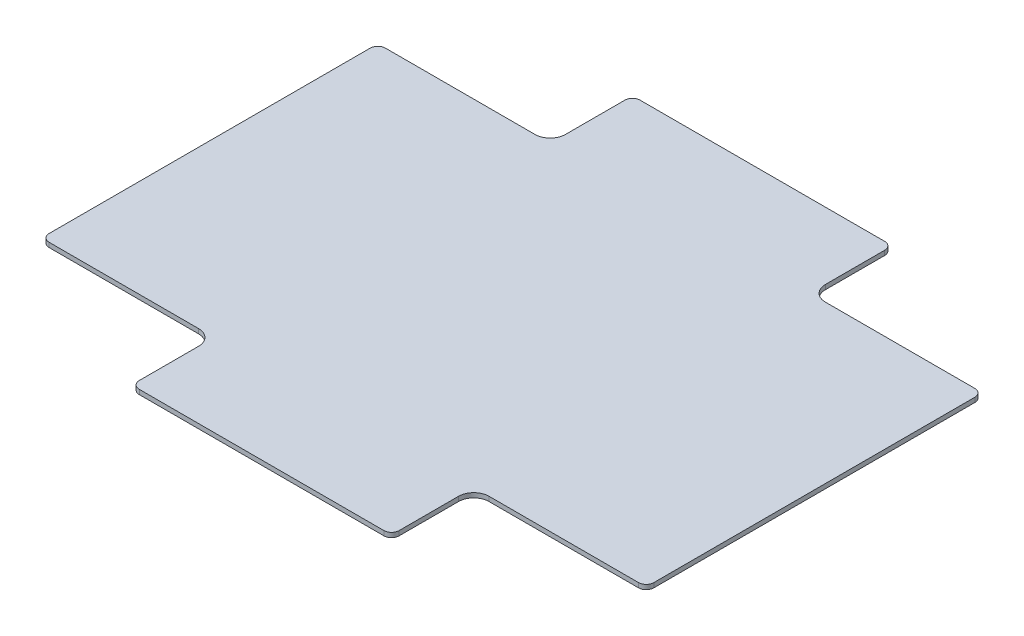
SolidWorks part; units mm, degrees
material "7075-T6, Пластина (SS)"
ref_plane "Спереди" through (0, 0, 0) normal (0, 0, 1) x (1, 0, 0)
ref_plane "Сверху" through (0, 0, 0) normal (0, 1, 0) x (1, 0, 0)
ref_plane "Справа" through (0, 0, 0) normal (1, 0, 0) x (0, 0, -1)
sketch "Эскиз1" plane through (0, 0, 0) normal (0, 1, 0) x (1, 0, 0)
  line L1 (-80, -163.8055) -> (80, -163.8055)
  line L2 (-197.7687, -105) -> (-197.7687, 105)
  line L3 (-80, 163.8055) -> (80, 163.8055)
  line L4 (197.7687, -105) -> (197.7687, 105)
  line L5 (-236.4266, 144.4996) -> (-147.9018, 144.4996) construction
  line L6 (-147.9018, 144.4996) -> (286.4952, 144.4996) construction
  line L18 (-284.5497, 0) -> (284.3305, 0) construction
  line L19 (-160.9018, 110) -> (-134.9018, 110)
  line L20 (-160.9018, 110) -> (-160.9018, 0)
  line L21 (-160.9018, 0) -> (-134.9018, 0)
  line L22 (-134.9018, 110) -> (-134.9018, 0)
  line L23 (-147.9018, -182.6295) -> (-147.9018, 219.9923) construction
  line L24 (-160.9018, 0) -> (-134.9018, 0)
  line L25 (-160.9018, 0) -> (-160.9018, -110)
  line L26 (-160.9018, -110) -> (-134.9018, -110)
  line L27 (-134.9018, 0) -> (-134.9018, -110)
  line L28 (-97.9018, -119.4996) -> (-197.9018, -119.4996)
  line L29 (-97.9018, 169.4996) -> (-197.9018, 169.4996)
  line L30 (-97.9018, 169.4996) -> (-97.9018, 119.4996)
  line L31 (-97.9018, 119.4996) -> (-197.9018, 119.4996)
  line L32 (-197.9018, 169.4996) -> (-197.9018, 119.4996)
  line L33 (-97.9018, 169.4996) -> (-197.9018, 119.4996) construction
  line L34 (-97.9018, 119.4996) -> (-197.9018, 169.4996) construction
  line L35 (-197.9018, -169.4996) -> (-197.9018, -119.4996)
  line L36 (-97.9018, -169.4996) -> (-197.9018, -169.4996)
  line L37 (-97.9018, -169.4996) -> (-97.9018, -119.4996)
  line L39 (-85, 120) -> (-85, 158.8055)
  line L40 (0, 262.7398) -> (0, -186.5795) construction
  line L41 (-192.7687, 110) -> (-95, 110)
  line L43 (-192.7687, -110) -> (-95, -110)
  line L44 (-85, -120) -> (-85, -158.8055)
  line L45 (85, 120) -> (85, 158.8055)
  line L46 (192.7687, 110) -> (95, 110)
  line L47 (192.7687, -110) -> (95, -110)
  line L48 (85, -120) -> (85, -158.8055)
  line L49 (97.9018, -169.4996) -> (97.9018, -119.4996)
  line L50 (97.9018, -169.4996) -> (197.9018, -169.4996)
  line L51 (197.9018, -169.4996) -> (197.9018, -119.4996)
  line L52 (97.9018, -119.4996) -> (197.9018, -119.4996)
  line L53 (160.9018, 0) -> (160.9018, -110)
  line L54 (160.9018, -110) -> (134.9018, -110)
  line L55 (134.9018, 0) -> (134.9018, -110)
  line L56 (160.9018, 0) -> (134.9018, 0)
  line L57 (160.9018, 110) -> (160.9018, 0)
  line L58 (160.9018, 0) -> (134.9018, 0)
  line L59 (134.9018, 110) -> (134.9018, 0)
  line L60 (160.9018, 110) -> (134.9018, 110)
  line L61 (97.9018, 119.4996) -> (197.9018, 119.4996)
  line L62 (197.9018, 169.4996) -> (197.9018, 119.4996)
  line L63 (97.9018, 169.4996) -> (197.9018, 169.4996)
  line L64 (97.9018, 169.4996) -> (97.9018, 119.4996)
  arc A0 (85, -120) -> (95, -110) centre (95, -120) cw
  arc A1 (85, 120) -> (95, 110) centre (95, 120) ccw
  arc A2 (-95, -110) -> (-85, -120) centre (-95, -120) cw
  arc A3 (-85, 120) -> (-95, 110) centre (-95, 120) cw
  arc A4 (192.7687, -110) -> (197.7687, -105) centre (192.7687, -105) ccw
  arc A5 (85, -158.8055) -> (80, -163.8055) centre (80, -158.8055) cw
  arc A6 (-85, -158.8055) -> (-80, -163.8055) centre (-80, -158.8055) ccw
  arc A7 (-192.7687, -110) -> (-197.7687, -105) centre (-192.7687, -105) cw
  arc A8 (-192.7687, 110) -> (-197.7687, 105) centre (-192.7687, 105) ccw
  arc A9 (197.7687, 105) -> (192.7687, 110) centre (192.7687, 105) ccw
  arc A10 (85, 158.8055) -> (80, 163.8055) centre (80, 158.8055) ccw
  arc A11 (-85, 158.8055) -> (-80, 163.8055) centre (-80, 158.8055) cw
  point P0 (0, 0)
  point P3 (85, -110)
  point P17 (-147.9018, 110)
  point P18 (-147.9018, 110)
  point P20 (-147.9018, 0)
  point P22 (-150, 134)
  point P37 (-147.9018, 144.4996)
  point P46 (85, 110)
  point P52 (-85, -110)
  point P55 (-85, 110)
  point P56 (-147.9018, 0)
  point P77 (197.7687, -110)
  point P80 (85, -163.8055)
  point P83 (-85, -163.8055)
  point P86 (-197.7687, -110)
  point P89 (-197.7687, 110)
  point P92 (197.7687, 110)
  point P95 (85, 163.8055)
  point P98 (-85, 163.8055)
  dimension "D2" = 50
  dimension "D6" = 10
  dimension "D4" = 5
  dimension "D3" = 26
  dimension "D5" = 338.9991
  dimension "D7" = 395.5373
  dimension "D8" = 110
  dimension "D9" = 170
  dimension "D10" = 100
  dimension "D13" = 9.4996
  dimension "D14" = 12.9018
sketch "Эскиз2" plane through (0, 0, 0) normal (0, 1, 0) x (1, 0, 0)
  line L0 (-162.9105, 114) -> (-136.9105, 114)
  line L1 (-162.9105, 114) -> (-162.9105, 0)
  line L2 (-162.9105, 0) -> (-136.9105, 0)
  line L3 (-136.9105, 114) -> (-136.9105, 0)
  line L4 (-149.9105, -192.6295) -> (-149.9105, 209.9923) construction
  line L5 (-162.9105, 0) -> (-136.9105, 0)
  line L6 (-162.9105, 0) -> (-162.9105, -114)
  line L7 (-162.9105, -114) -> (-136.9105, -114)
  line L8 (-136.9105, 0) -> (-136.9105, -114)
  line L9 (-99.9105, -123.5568) -> (-199.9105, -123.5568)
  line L10 (-99.9105, 163.4996) -> (-199.9105, 163.4996)
  line L11 (-99.9105, 163.4996) -> (-99.9105, 123.4996)
  line L12 (-99.9105, 123.4996) -> (-199.9105, 123.4996)
  line L13 (-199.9105, 163.4996) -> (-199.9105, 123.4996)
  line L14 (-199.9105, -163.5568) -> (-199.9105, -123.5568)
  line L15 (-99.9105, -163.5568) -> (-199.9105, -163.5568)
  line L16 (-99.9105, -163.5568) -> (-99.9105, -123.5568)
  line L17 (-284.5497, 0) -> (284.3305, 0) construction
  point P11 (-149.9105, 0)
  point P12 (-149.9105, 0)
sketch "Эскиз3" plane through (0, 0, 0) normal (0, 1, 0) x (1, 0, 0)
  line L0 (-89.8176, -177.9027) -> (70.2405, -177.9027)
  line L1 (-209.7886, -106.9112) -> (-209.7886, 106.8353)
  line L2 (-80.029, 172.0973) -> (50.2405, 172.0973)
  line L3 (170.2114, -106.9112) -> (170.2114, 103.9123)
  line L4 (-87.1938, 124.0033) -> (-87.1938, 164.9326)
  line L5 (-202.6239, 114) -> (-97.1971, 114)
  line L6 (-202.6239, -114.076) -> (-106.9857, -114.076)
  line L7 (-96.9823, -124.0793) -> (-96.9823, -170.738)
  line L8 (57.4052, 121.0803) -> (57.4052, 164.9326)
  line L9 (163.0467, 111.077) -> (67.4085, 111.077)
  line L10 (163.0467, -114.076) -> (87.4085, -114.076)
  line L11 (77.4052, -124.0793) -> (77.4052, -170.738)
  line L13 (-162.9105, 114) -> (-136.9105, 114) construction
  arc A0 (77.4052, -124.0793) -> (87.4085, -114.076) centre (87.4085, -124.0793) cw
  arc A1 (57.4052, 121.0803) -> (67.4085, 111.077) centre (67.4085, 121.0803) ccw
  arc A2 (-106.9857, -114.076) -> (-96.9823, -124.0793) centre (-106.9857, -124.0793) cw
  arc A3 (-87.1938, 124.0033) -> (-97.1971, 114) centre (-97.1971, 124.0033) cw
  arc A4 (-80.029, 172.0973) -> (-87.1938, 164.9326) centre (-80.029, 164.9326) ccw
  arc A5 (50.2405, 172.0973) -> (57.4052, 164.9326) centre (50.2405, 164.9326) cw
  arc A6 (170.2114, 103.9123) -> (163.0467, 111.077) centre (163.0467, 103.9123) ccw
  arc A7 (170.2114, -106.9112) -> (163.0467, -114.076) centre (163.0467, -106.9112) cw
  arc A8 (70.2405, -177.9027) -> (77.4052, -170.738) centre (70.2405, -170.738) ccw
  arc A9 (-89.8176, -177.9027) -> (-96.9823, -170.738) centre (-89.8176, -170.738) cw
  arc A10 (-209.7886, -106.9112) -> (-202.6239, -114.076) centre (-202.6239, -106.9112) ccw
  arc A11 (-209.7886, 106.8353) -> (-202.6239, 114) centre (-202.6239, 106.8353) cw
  point P36 (115.2276, 111.077)
  point P39 (-149.9105, 114)
  point P42 (-149.9105, 114)
  dimension "D3" = 10.0033
  dimension "D4" = 7.1647
  dimension "D1" = 380
  dimension "D2" = 350
  dimension "D5" = 112.8062
  dimension "D6" = 63.8267
  dimension "D7" = 61.0203
extrude "Бобышка-Вытянуть1" add sketch "Эскиз1" along normal blind 3 separate body contours A11 L39 A3 L41 L22 L27 L43 A2 L44 A6 L1 A5 L48 A0 L47 L55 L59 L46 A1 L45 A10 L3 | L4 A9 L46 L57 L53 L47 A4 | L46 L59 L56 L57 | L53 L56 L55 L47 | L27 L21 L25 L26 | L41 A8 L2 A7 L43 L25 L20 | L22 L19 L20 L21 region at (0, 0, 0) region at (-147.9018, 0, 55) region at (147.9018, 0, 55) region at (-179.3123, 0, 0) region at (-147.9018, 0, -55) region at (179.3123, 0, 0) region at (147.9018, 0, -55)
